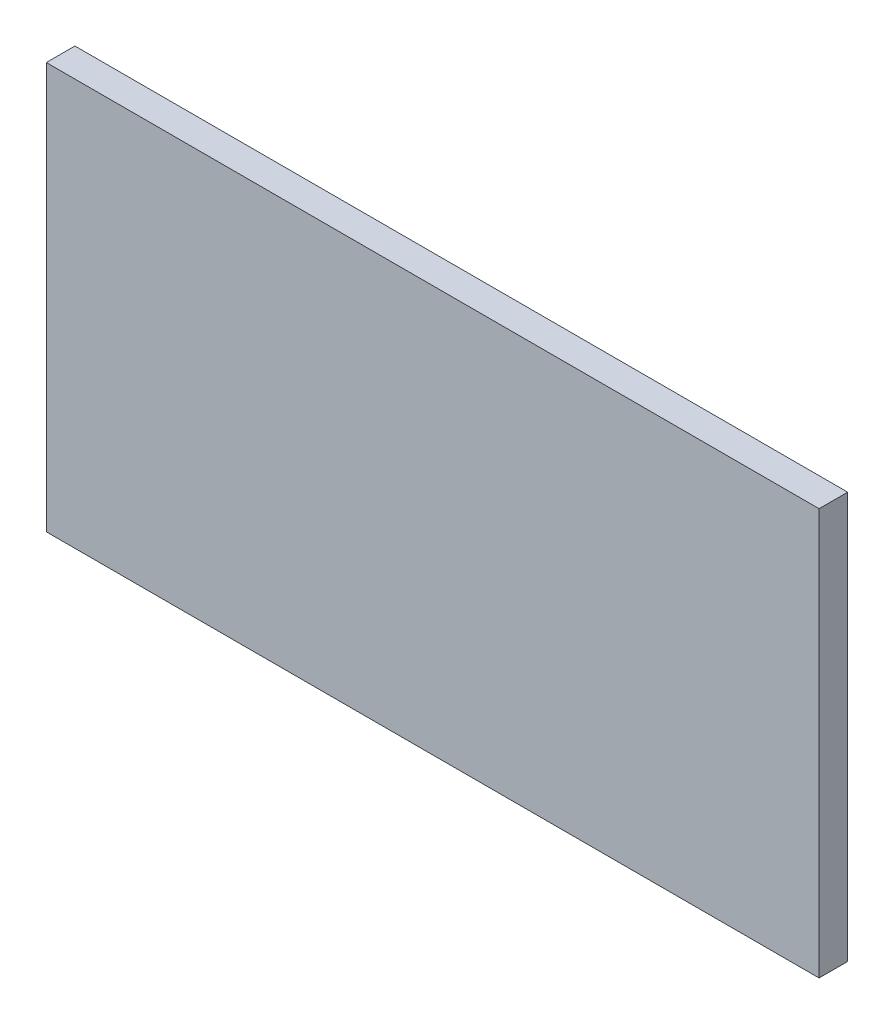
SolidWorks part; units mm, degrees
ref_plane "Front Plane" through (0, 0, 0) normal (0, 0, 1) x (1, 0, 0)
ref_plane "Top Plane" through (0, 0, 0) normal (0, 1, 0) x (1, 0, 0)
ref_plane "Right Plane" through (0, 0, 0) normal (1, 0, 0) x (0, 0, -1)
sketch "Sketch1" plane through (0, 0, 0) normal (0, 0, 1) x (1, 0, 0)
  line L1 (135, -71) -> (-135, -71)
  line L2 (135, -71) -> (135, 71)
  line L3 (135, 71) -> (-135, 71)
  line L4 (-135, -71) -> (-135, 71)
  line L5 (135, -71) -> (-135, 71) construction
  line L6 (135, 71) -> (-135, -71) construction
  point P0 (0, 0)
  dimension "D1" = 270
  dimension "D2" = 142
extrude "Boss-Extrude1" add sketch "Sketch1" along normal mid plane 10
